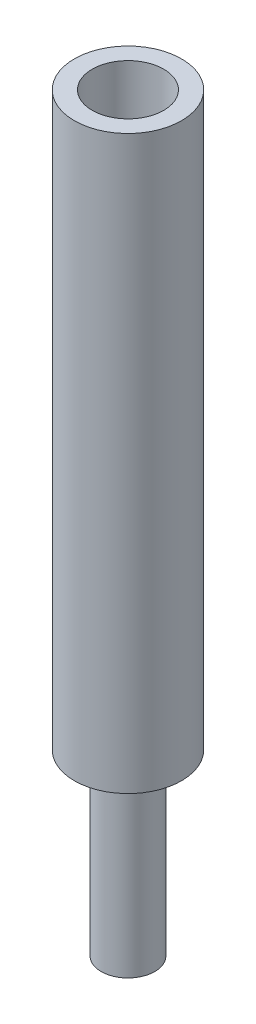
SolidWorks part; units mm, degrees
ref_plane "Front Plane" through (0, 0, 0) normal (0, 0, 1) x (1, 0, 0)
ref_plane "Top Plane" through (0, 0, 0) normal (0, 1, 0) x (1, 0, 0)
ref_plane "Right Plane" through (0, 0, 0) normal (1, 0, 0) x (0, 0, -1)
sketch "Sketch1" plane through (0, 0, 0) normal (0, 1, 0) x (1, 0, 0)
  circle A0 centre (0, 0) radius 1.5
  circle A1 centre (0, 0) radius 3
  circle A2 centre (0, 0) radius 2
  dimension "D1" = 3
  dimension "D2" = 6
  dimension "D3" = 4
extrude "Boss-Extrude1" add sketch "Sketch1" along normal blind 10 contours A0 region at (0, 0, 0)
extrude "Boss-Extrude2" add sketch "Sketch1<3>" along normal blind 2 from surface contours A1 A2 | A1 region at (-2.9151, 0, 0) starting at face at (0, 10, 1.5)
sketch "Sketch1<3>" plane through (0, 0, 0) normal (0, 1, 0) x (1, 0, 0) same geometry as "Sketch1"
extrude "Boss-Extrude3" add sketch "Sketch1<4>" along normal blind 30 from surface contours A1 A2 region at (-2.9151, 0, 0) starting at face at (0, 12, 3)
sketch "Sketch1<4>" plane through (0, 0, 0) normal (0, 1, 0) x (1, 0, 0) same geometry as "Sketch1"
